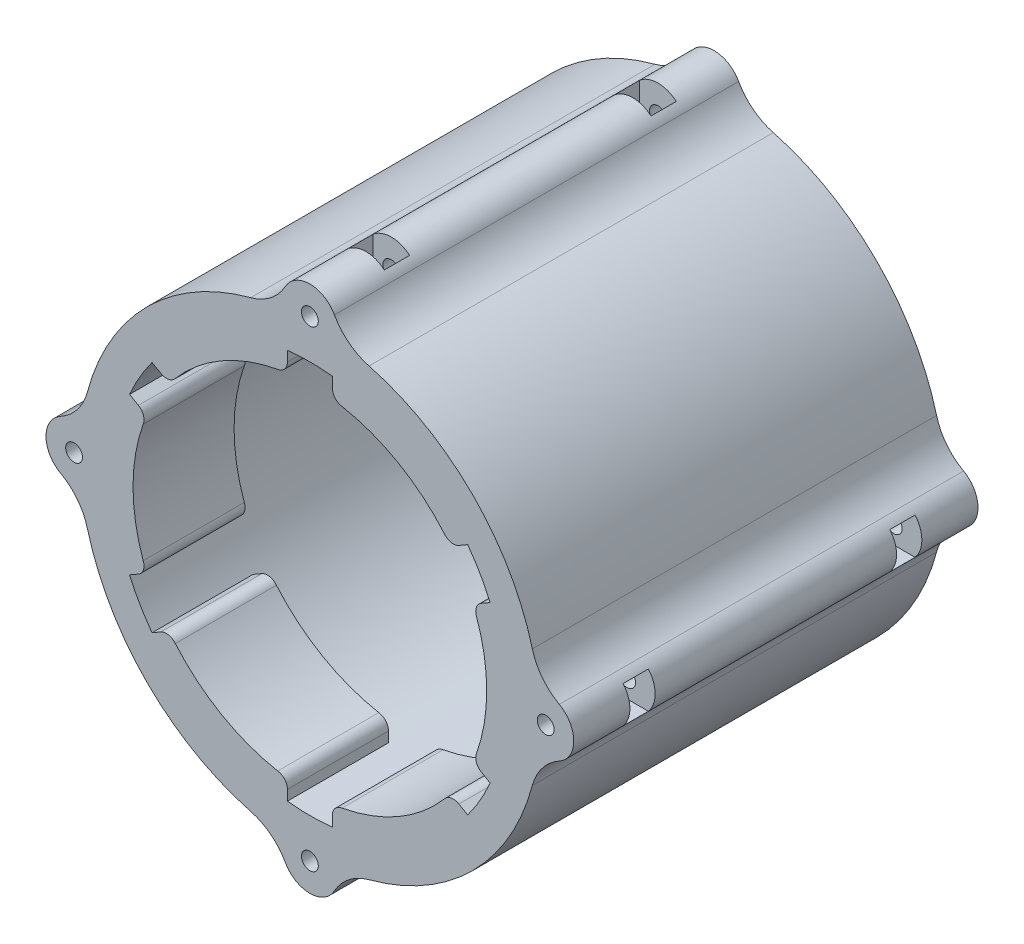
SolidWorks part; units mm, degrees
ref_plane "Ön Düzlem" through (0, 0, 0) normal (0, 0, 1) x (1, 0, 0)
ref_plane "Üst Düzlem" through (0, 0, 0) normal (0, 1, 0) x (1, 0, 0)
ref_plane "Sağ Düzlem" through (0, 0, 0) normal (1, 0, 0) x (0, 0, -1)
sketch "Çizim1" plane through (0, 0, 0) normal (0, 0, 1) x (1, 0, 0)
  circle A0 centre (0, 0) radius 35
  arc A1 (-39.6218, -10.5408) -> (-10.5408, -39.6218) centre (0, 0) ccw
  circle A6 centre (-42, 0) radius 1.5
  arc A7 (-44.4286, 4.3706) -> (-44.4286, -4.3706) centre (-42, 0) ccw
  circle A8 centre (0, 0) radius 41 construction
  arc A9 (-39.6218, -10.5408) -> (-44.4286, -4.3706) centre (-49.2857, -13.1118) ccw
  arc A10 (-39.6218, 10.5408) -> (-44.4286, 4.3706) centre (-49.2857, 13.1118) cw
  circle A11 centre (0, 42) radius 1.5
  arc A12 (4.3706, 44.4286) -> (-4.3706, 44.4286) centre (0, 42) ccw
  arc A13 (-10.5408, 39.6218) -> (-4.3706, 44.4286) centre (-13.1118, 49.2857) ccw
  arc A14 (10.5408, 39.6218) -> (4.3706, 44.4286) centre (13.1118, 49.2857) cw
  circle A15 centre (42, 0) radius 1.5
  arc A16 (44.4286, -4.3706) -> (44.4286, 4.3706) centre (42, 0) ccw
  arc A17 (39.6218, 10.5408) -> (44.4286, 4.3706) centre (49.2857, 13.1118) ccw
  arc A18 (39.6218, -10.5408) -> (44.4286, -4.3706) centre (49.2857, -13.1118) cw
  circle A19 centre (0, -42) radius 1.5
  arc A20 (-4.3706, -44.4286) -> (4.3706, -44.4286) centre (0, -42) ccw
  arc A21 (10.5408, -39.6218) -> (4.3706, -44.4286) centre (13.1118, -49.2857) ccw
  arc A22 (-10.5408, -39.6218) -> (-4.3706, -44.4286) centre (-13.1118, -49.2857) cw
  arc A23 (-10.5408, 39.6218) -> (-39.6218, 10.5408) centre (0, 0) ccw
  arc A24 (39.6218, 10.5408) -> (10.5408, 39.6218) centre (0, 0) ccw
  arc A25 (10.5408, -39.6218) -> (39.6218, -10.5408) centre (0, 0) ccw
  point P16 (0, 0)
  point P41 (0, 0)
  dimension "D1" = 70
  dimension "D3" = 5
  dimension "D4" = 3
  dimension "D5" = 42
  dimension "D6" = 10
  dimension "D2" = 6
  dimension "D7" = 4
extrude "Yükseklik-Ekstrüzyon1" add sketch "Çizim1" along normal blind 72
sketch "Çizim2" plane through (0, 0, 72) normal (0, 0, 1) x (1, 0, 0)
  line L0 (-4, 34.7707) -> (-4, 32.9563)
  line L1 (4, 34.7707) -> (4, 32.9563)
  line L2 (28.1123, 20.8494) -> (26.541, 19.9422)
  line L3 (32.1123, 13.9212) -> (30.541, 13.014)
  line L4 (32.1123, -13.9212) -> (30.541, -13.014)
  line L5 (28.1123, -20.8494) -> (26.541, -19.9422)
  line L6 (4, -34.7707) -> (4, -32.9563)
  line L7 (-4, -34.7707) -> (-4, -32.9563)
  line L8 (-28.1123, -20.8494) -> (-26.541, -19.9422)
  line L9 (-32.1123, -13.9212) -> (-30.541, -13.014)
  line L10 (-32.1123, 13.9212) -> (-30.541, 13.014)
  line L11 (-28.1123, 20.8494) -> (-26.541, 19.9422)
  arc A0 (26.541, 19.9422) -> (23.9615, 20.4474) centre (25.541, 21.6743) cw
  arc A3 (-4, 34.7707) -> (-28.1123, 20.8494) centre (0, 0) ccw
  arc A5 (4, 32.9563) -> (5.7273, 30.975) centre (6, 32.9563) ccw
  arc A6 (-4, 32.9563) -> (-5.7273, 30.975) centre (-6, 32.9563) cw
  arc A19 (-5.7273, 30.975) -> (-23.9615, 20.4474) centre (0, 0) ccw
  arc A20 (30.541, 13.014) -> (29.6887, 10.5275) centre (31.541, 11.282) ccw
  arc A21 (30.541, -13.014) -> (29.6887, -10.5275) centre (31.541, -11.282) cw
  arc A22 (26.541, -19.9422) -> (23.9615, -20.4474) centre (25.541, -21.6743) ccw
  arc A23 (4, -32.9563) -> (5.7273, -30.975) centre (6, -32.9563) cw
  arc A24 (-4, -32.9563) -> (-5.7273, -30.975) centre (-6, -32.9563) ccw
  arc A25 (-26.541, -19.9422) -> (-23.9615, -20.4474) centre (-25.541, -21.6743) cw
  arc A26 (-30.541, -13.014) -> (-29.6887, -10.5275) centre (-31.541, -11.282) ccw
  arc A27 (-30.541, 13.014) -> (-29.6887, 10.5275) centre (-31.541, 11.282) cw
  arc A28 (-26.541, 19.9422) -> (-23.9615, 20.4474) centre (-25.541, 21.6743) ccw
  circle A29 centre (0, 0) radius 35 construction
  circle A30 centre (0, 0) radius 31.5 construction
  arc A31 (28.1123, 20.8494) -> (4, 34.7707) centre (0, 0) ccw
  arc A32 (23.9615, 20.4474) -> (5.7273, 30.975) centre (0, 0) ccw
  arc A33 (29.6887, -10.5275) -> (29.6887, 10.5275) centre (0, 0) ccw
  arc A34 (32.1123, -13.9212) -> (32.1123, 13.9212) centre (0, 0) ccw
  arc A35 (5.7273, -30.975) -> (23.9615, -20.4474) centre (0, 0) ccw
  arc A36 (4, -34.7707) -> (28.1123, -20.8494) centre (0, 0) ccw
  arc A37 (-23.9615, -20.4474) -> (-5.7273, -30.975) centre (0, 0) ccw
  arc A38 (-28.1123, -20.8494) -> (-4, -34.7707) centre (0, 0) ccw
  arc A39 (-29.6887, 10.5275) -> (-29.6887, -10.5275) centre (0, 0) ccw
  arc A40 (-32.1123, 13.9212) -> (-32.1123, -13.9212) centre (0, 0) ccw
  point P55 (0, 0)
  dimension "D2" = 3.5
  dimension "D4" = 2
  dimension "D1" = 70
  dimension "D6" = 1.8144
  dimension "D3" = 4
  dimension "D5" = 4
  dimension "D7" = 1.8144
  dimension "D8" = 6
extrude "Yükseklik-Ekstrüzyon2" add sketch "Çizim2" against normal blind 18
ref_plane "Düzlem1" through (0, 0, 10) normal (0, 0, -1) x (-1, 0, 0)
sketch "Çizim3" plane through (0, 0, 10) normal (0, 0, -1) x (-1, 0, 0)
  line L0 (-3.262, -42) -> (-3.262, -48)
  line L1 (3.262, -42) -> (1.631, -39.175)
  line L2 (1.631, -39.175) -> (-1.631, -39.175)
  line L3 (-1.631, -39.175) -> (-3.262, -42)
  line L7 (3.262, -42) -> (3.262, -48)
  line L8 (3.262, -48) -> (-3.262, -48)
  line L9 (-2.4465, -43.4125) -> (-1.631, -44.825) [skipped]
  line L10 (0, -44.825) -> (1.631, -44.825) [skipped]
  line L11 (2.4465, -43.4125) -> (3.262, -42) [skipped]
  circle A0 centre (0, -42) radius 2.825 construction
  dimension "D1" = 3.262
  dimension "D2" = 6
  dimension "D3" = 6
  dimension "D4" = 3.262
  dimension "D5" = 3.262
extrude "Kes-Ekstrüzyon1" cut sketch "Çizim3" against normal blind 4.5
pattern_circular "Dairesel Kaplama1" count 4 every 90 about axis through (0, 0, 0) along (0, 0, 1) of "Kes-Ekstrüzyon1"
ref_plane "Düzlem2" through (0, 0, 36) normal (0, 0, -1) x (-1, 0, 0)
mirror "Aynalama1" about plane through (0, 0, 36) normal (0, 0, -1) of "Dairesel Kaplama1"
